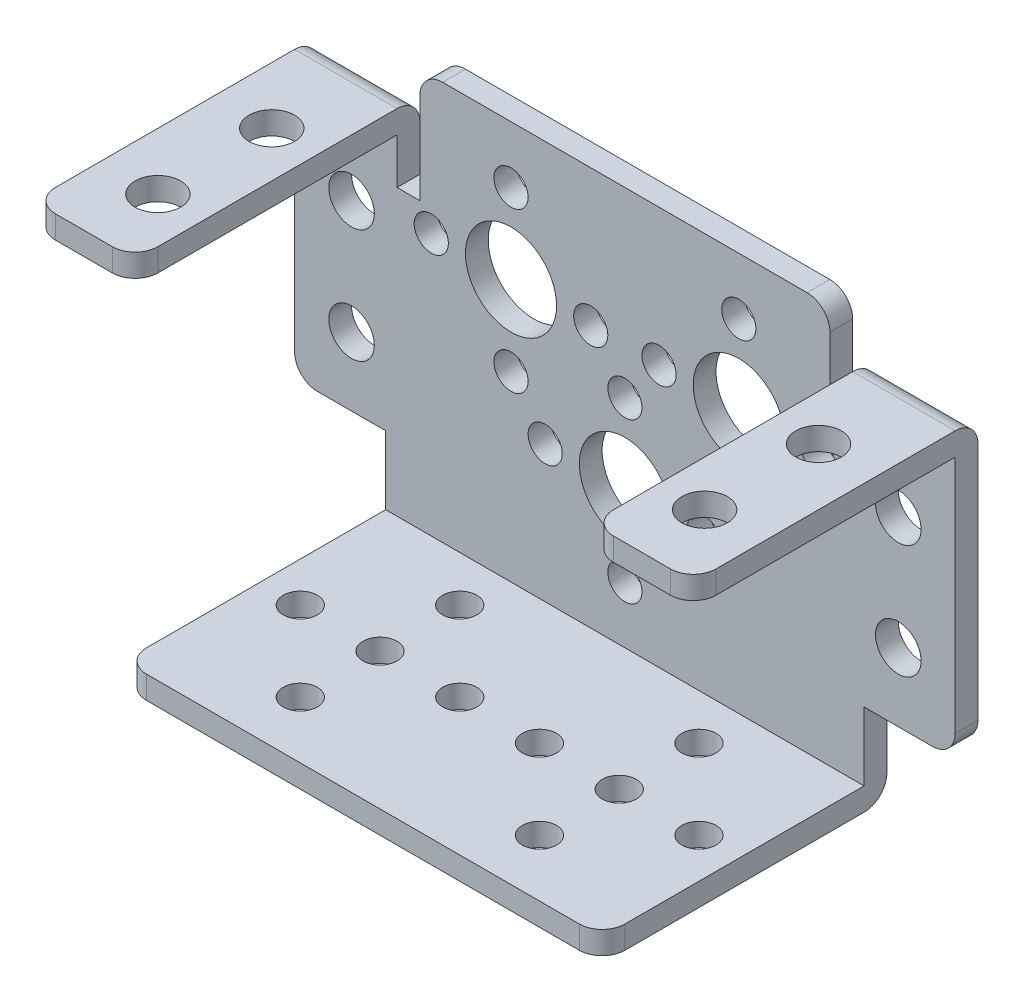
SolidWorks part; units mm, degrees
ref_plane "Front Plane" through (0, 0, 0) normal (0, 0, 1) x (1, 0, 0)
ref_plane "Top Plane" through (0, 0, 0) normal (0, 1, 0) x (1, 0, 0)
ref_plane "Right Plane" through (0, 0, 0) normal (1, 0, 0) x (0, 0, -1)
sketch "Sketch1" plane through (0, 0, 0) normal (0, 0, 1) x (1, 0, 0)
  line L0 (-21, -18.5) -> (21, -18.5)
  line L2 (29, -8.5) -> (29, 14.5)
  line L3 (16, 18.5) -> (-16, 18.5)
  line L4 (-29, -8.5) -> (-29, 14.5)
  line L7 (-21, -16.5) -> (-21, -18.5)
  line L8 (-21, -16.5) -> (-21, -10.5)
  line L9 (-21, -10.5) -> (-27, -10.5)
  line L10 (21, -16.5) -> (21, -10.5)
  line L11 (21, -10.5) -> (27, -10.5)
  line L12 (21, -16.5) -> (21, -18.5)
  line L13 (-21, -16.5) -> (21, -16.5)
  line L14 (0, 0) -> (0, -16.5) construction
  line L15 (29, 14.5) -> (20, 14.5)
  line L16 (18, 14.5) -> (18, 16.5)
  line L17 (-18, 16.5) -> (-18, 14.5)
  line L18 (-20, 14.5) -> (-29, 14.5)
  line L19 (-18, 14.5) -> (-18, 8.5)
  line L20 (-18, 8.5) -> (-20, 8.5)
  line L21 (-20, 8.5) -> (-20, 14.5)
  line L22 (18, 14.5) -> (18, 8.5)
  line L23 (18, 8.5) -> (20, 8.5)
  line L24 (20, 8.5) -> (20, 14.5)
  line L25 (20, 12.5) -> (29, 12.5)
  line L26 (-29, 12.5) -> (-20, 12.5)
  arc A0 (-18, 16.5) -> (-16, 18.5) centre (-16, 16.5) cw
  arc A1 (18, 16.5) -> (16, 18.5) centre (16, 16.5) ccw
  arc A2 (27, -10.5) -> (29, -8.5) centre (27, -8.5) ccw
  arc A3 (-27, -10.5) -> (-29, -8.5) centre (-27, -8.5) cw
  point P0 (0, 0)
  dimension "D1" = 2
extrude "Boss-Extrude1" add sketch "Sketch1" against normal blind 2 contours A3 L9 L8 L13 L10 L11 A2 L2 L25 L24 L23 L22 L16 A1 L3 A0 L17 L19 L20 L21 L26 L4 | L4 L26 L21 L18 | L24 L25 L2 L15 | L13 L7 L0 L12 region at (0, -17.5, 0) region at (0, 0.6161, 0) region at (-24.5, 13.5, 0) region at (24.5, 13.5, 0)
extrude "Boss-Extrude2" add sketch "Sketch1<3>" along normal blind 23 contours L13 L7 L0 L12 | L4 L26 L21 L18 | L24 L25 L2 L15 region at (0, -17.5, 0) region at (-24.5, 13.5, 0) region at (24.5, 13.5, 0)
sketch "Sketch1<3>" plane through (0, 0, 0) normal (0, 0, 1) x (1, 0, 0) same geometry as "Sketch1"
fillet "Fillet1" radius 2 9 edges at (0, -18.5, -2) (24.5, 14.5, -2) (-24.5, 14.5, -2) (-29, 13.5, 23) (-20, 13.5, 23) (20, 13.5, 23) (29, 13.5, 23) (-21, -17.5, 23) (21, -17.5, 23)
sketch "Sketch2" plane through (0, -16.5, 0) normal (0, 1, 0) x (1, 0, 0)
  line L0 (0, -23) -> (0, 0) construction
  line L1 (-19, -23) -> (19, -23) construction
  line L2 (-21, 0) -> (21, 0) construction
  line L3 (21, -10.5) -> (19, -10.5) construction
  line L4 (21, -21) -> (21, 0) construction
  line L5 (19, 0) -> (19, -23) construction
  line L6 (17.5, -11) -> (17.5, 0) construction
  line L7 (17.5, -11) -> (10.5, -11) construction
  circle A1 centre (17.5, -11) radius 1.5
  circle A2 centre (10.5, -11) radius 1.5
  circle A3 centre (10.5, -18) radius 1.5
  circle A4 centre (3.5, -11) radius 1.5
  circle A5 centre (10.5, -4) radius 1.5
  circle A7 centre (-17.5, -11) radius 1.5
  circle A8 centre (-10.5, -18) radius 1.5
  circle A9 centre (-10.5, -11) radius 1.5
  circle A10 centre (-3.5, -11) radius 1.5
  circle A11 centre (-10.5, -4) radius 1.5
  point P13 (19, -10.5)
  dimension "D1" = 4
extrude "Cut-Extrude1" cut sketch "Sketch2" against normal blind 25
sketch "Sketch3" plane through (0, 0, 0) normal (0, 0, 1) x (1, 0, 0)
  line L0 (0, 18.5) -> (0, -16.5) construction
  line L1 (16, 18.5) -> (-16, 18.5) construction
  line L2 (-21, -16.5) -> (21, -16.5) construction
  line L3 (-24, 12.5) -> (-24, -10.5) construction
  line L4 (-29, 12.5) -> (-20, 12.5) construction
  line L5 (-21, -10.5) -> (-27, -10.5) construction
  line L6 (-29, -8.5) -> (-29, 12.5) construction
  line L7 (-10, 6.5) -> (-3, 6.5) construction
  line L9 (-10, 18.5) -> (-10, -16.5) construction
  circle A0 centre (-24, -4.5) radius 2
  circle A1 centre (-24, 5.5) radius 2
  circle A2 centre (-10, 6.5) radius 4
  circle A3 centre (-3, 6.5) radius 1.5
  circle A4 centre (-10, -0.5) radius 1.5
  circle A5 centre (-17, 6.5) radius 1.5
  circle A6 centre (-10, 13.5) radius 1.5
  circle A7 centre (10, -0.5) radius 1.5
  circle A8 centre (3, 6.5) radius 1.5
  circle A9 centre (10, 13.5) radius 1.5
  circle A10 centre (10, 6.5) radius 4
  circle A11 centre (17, 6.5) radius 1.5
  circle A12 centre (24, -4.5) radius 2
  circle A13 centre (24, 5.5) radius 2
  circle A14 centre (0, -4.5) radius 4
  circle A15 centre (0, -4.5) radius 7 construction
  circle A16 centre (0, -11.5) radius 1.5
  circle A17 centre (-7, -4.5) radius 1.5
  circle A18 centre (0, 2.5) radius 1.5
  circle A19 centre (7, -4.5) radius 1.5
  dimension "D3" = 10
  dimension "D6" = 4
  dimension "D7" = 23
  dimension "D8" = 4
  dimension "D1" = 5
  dimension "D2" = 6
  dimension "D4" = 10
  dimension "D5" = 12
extrude "Cut-Extrude2" cut sketch "Sketch3" against normal blind 25
sketch "Sketch4" plane through (0, 14.5, 0) normal (0, 1, 0) x (1, 0, 0)
  line L0 (-24, 2) -> (-24, -7) construction
  line L2 (-24, -7) -> (-20, -7) construction
  line L3 (-20, 0) -> (-20, -21) construction
  line L4 (-24, -7) -> (-24, -17) construction
  line L5 (0, -13.75) -> (0, 13.75) construction
  circle A0 centre (-24, -7) radius 2
  circle A1 centre (-24, -17) radius 2
  circle A2 centre (24, -17) radius 2
  circle A3 centre (24, -7) radius 2
extrude "Cut-Extrude3" cut sketch "Sketch4" against normal blind 25
